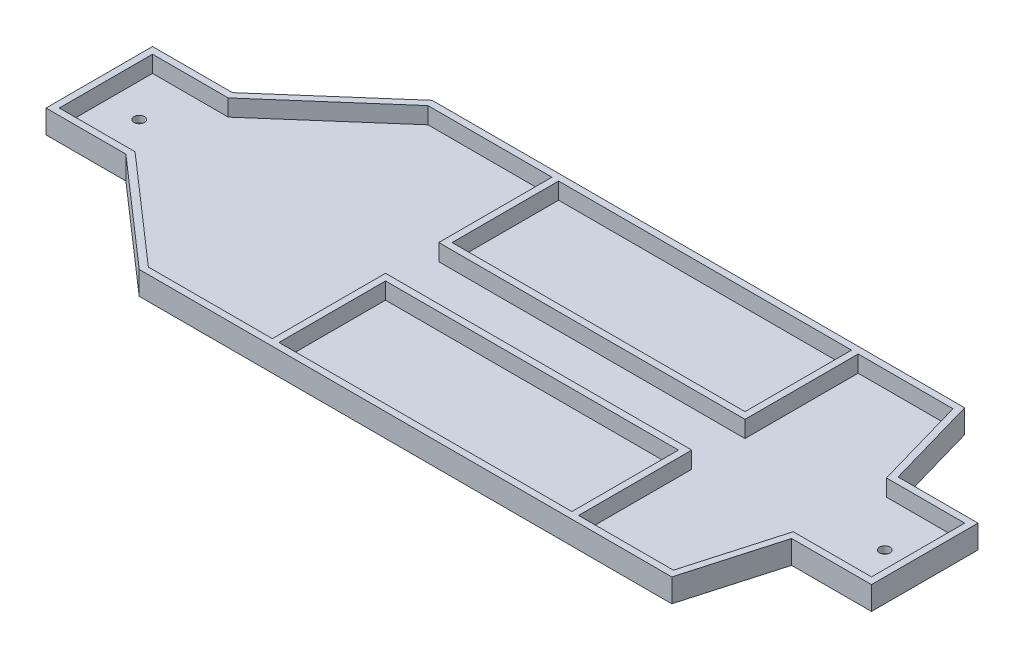
SolidWorks part; units mm, degrees
ref_plane "Front Plane" through (0, 0, 0) normal (0, 0, 1) x (1, 0, 0)
ref_plane "Top Plane" through (0, 0, 0) normal (0, 1, 0) x (1, 0, 0)
ref_plane "Right Plane" through (0, 0, 0) normal (1, 0, 0) x (0, 0, -1)
sketch "Sketch1" plane through (0, 0, 0) normal (0, 1, 0) x (1, 0, 0)
  line L0 (-127, 69.85) -> (-177.8, 25.4)
  line L1 (-127, 69.85) -> (127, 69.85)
  line L2 (-127, 69.85) -> (-127, -69.85) construction
  line L3 (-127, -69.85) -> (127, -69.85)
  line L4 (127, 69.85) -> (127, -69.85) construction
  line L5 (-127, 69.85) -> (127, -69.85) construction
  line L6 (-127, -69.85) -> (127, 69.85) construction
  line L7 (-177.8, 25.4) -> (-215.9, 25.4)
  line L8 (-215.9, 25.4) -> (-215.9, -25.4)
  line L9 (-215.9, -25.4) -> (-177.8, -25.4)
  line L10 (-177.8, -25.4) -> (-127, -69.85)
  line L11 (127, -69.85) -> (139.7, -25.4)
  line L12 (139.7, -25.4) -> (177.8, -25.4)
  line L13 (177.8, -25.4) -> (177.8, 25.4)
  line L14 (177.8, 25.4) -> (139.7, 25.4)
  line L15 (139.7, 25.4) -> (127, 69.85)
  line L16 (-215.9, 25.4) -> (-177.8, -25.4) construction
  line L17 (139.7, 25.4) -> (177.8, -25.4) construction
  line L18 (-125.807, 66.675) -> (-176.607, 22.225)
  line L19 (-63.5, -15.875) -> (76.2, -15.875)
  line L20 (-63.5, -15.875) -> (-63.5, -66.675)
  line L21 (-63.5, -66.675) -> (76.2, -66.675)
  line L22 (76.2, -15.875) -> (76.2, -66.675)
  line L23 (-63.5, -15.875) -> (76.2, -66.675) construction
  line L24 (-63.5, -66.675) -> (76.2, -15.875) construction
  line L25 (-63.5, 66.675) -> (76.2, 66.675)
  line L26 (-63.5, 66.675) -> (-63.5, 15.875)
  line L27 (-63.5, 15.875) -> (76.2, 15.875)
  line L28 (76.2, 66.675) -> (76.2, 15.875)
  line L29 (-63.5, 66.675) -> (76.2, 15.875) construction
  line L30 (-63.5, 15.875) -> (76.2, 66.675) construction
  line L31 (-176.607, 22.225) -> (-212.725, 22.225)
  line L32 (-212.725, 22.225) -> (-212.725, -22.225)
  line L33 (-212.725, -22.225) -> (-176.607, -22.225)
  line L34 (-176.607, -22.225) -> (-125.807, -66.675)
  line L35 (-125.807, -66.675) -> (124.6051, -66.675)
  line L36 (124.6051, -66.675) -> (137.3051, -22.225)
  line L37 (137.3051, -22.225) -> (174.625, -22.225)
  line L38 (174.625, -22.225) -> (174.625, 22.225)
  line L39 (174.625, 22.225) -> (137.3051, 22.225)
  line L40 (137.3051, 22.225) -> (124.6051, 66.675)
  line L41 (-125.807, 66.675) -> (124.6051, 66.675)
  line L42 (-66.675, 69.85) -> (-66.675, 12.7)
  line L43 (-66.675, 12.7) -> (79.375, 12.7)
  line L44 (79.375, 69.85) -> (79.375, 12.7)
  line L45 (-66.675, 69.85) -> (79.375, 69.85)
  line L46 (-66.675, -12.7) -> (79.375, -12.7)
  line L47 (79.375, -12.7) -> (79.375, -69.85)
  line L48 (-66.675, -69.85) -> (79.375, -69.85)
  line L49 (-66.675, -12.7) -> (-66.675, -69.85)
  circle A0 centre (-196.85, 0) radius 2.4892
  circle A1 centre (158.75, 0) radius 2.4892
  point P0 (0, 0)
  point P18 (6.35, -41.275)
  point P23 (6.35, 41.275)
  point P28 (2.9289, 38.1)
  dimension "D2" = 4.9784
  dimension "D1" = 254
  dimension "D3" = 355.6
  dimension "D4" = 139.7
  dimension "D5" = 50.8
  dimension "D6" = 3.175
  dimension "D7" = 3.175
  dimension "D8" = 139.7
  dimension "D9" = 50.8
  dimension "D10" = 50.8
  dimension "D11" = 50.8
  dimension "D12" = 50.8
  dimension "D13" = 88.9
  dimension "D14" = 3.175
  dimension "D15" = 3.175
extrude "Boss-Extrude1" add sketch "Sketch1" along normal blind 3.175 contours L49 L46 L47 L35 L36 L37 L38 L39 L40 L41 L44 L43 L42 L18 L31 L32 L33 L34 A1 A0 | L28 L25 L26 L27 | L22 L19 L20 L21 | L49 L35 L34 L33 L32 L31 L18 L41 L42 L1 L0 L7 L8 L9 L10 L3 | L46 L49 L35 L20 L19 L22 L47 | L35 L49 L3 L47 L21 | L35 L47 L3 L11 L12 L13 L14 L15 L1 L44 L41 L40 L39 L38 L37 L36 | L44 L1 L42 L41 L25 | L44 L41 L28 L27 L26 L42 L43 region at (-96.8375, 0, -67.8059) region at (6.35, 0, -68.2625) region at (103.1875, 0, -68.1411) region at (-26.0534, 0, 0) region at (-65.0875, 0, -65.118) region at (6.35, 0, -41.275) region at (6.35, 0, 68.2625) region at (-65.118, 0, 39.6875) region at (6.35, 0, 41.275)
extrude "Boss-Extrude2" add sketch "Sketch1<3>" along normal blind 11.1125 contours L49 L35 L34 L33 L32 L31 L18 L41 L42 L1 L0 L7 L8 L9 L10 L3 | L46 L49 L35 L20 L19 L22 L47 | L35 L49 L3 L47 L21 | L44 L1 L42 L41 L25 | L44 L41 L28 L27 L26 L42 L43 | L35 L47 L3 L11 L12 L13 L14 L15 L1 L44 L41 L40 L39 L38 L37 L36 region at (-96.8375, 0, -67.8059) region at (6.35, 0, -68.2625) region at (103.1875, 0, -68.1411) region at (-65.0875, 0, -65.118) region at (6.35, 0, 68.2625) region at (-65.118, 0, 39.6875)
sketch "Sketch1<3>" plane through (0, 0, 0) normal (0, 1, 0) x (1, 0, 0) same geometry as "Sketch1"
equation "\"D7@Sketch1\"=\"D6@Sketch1\""
